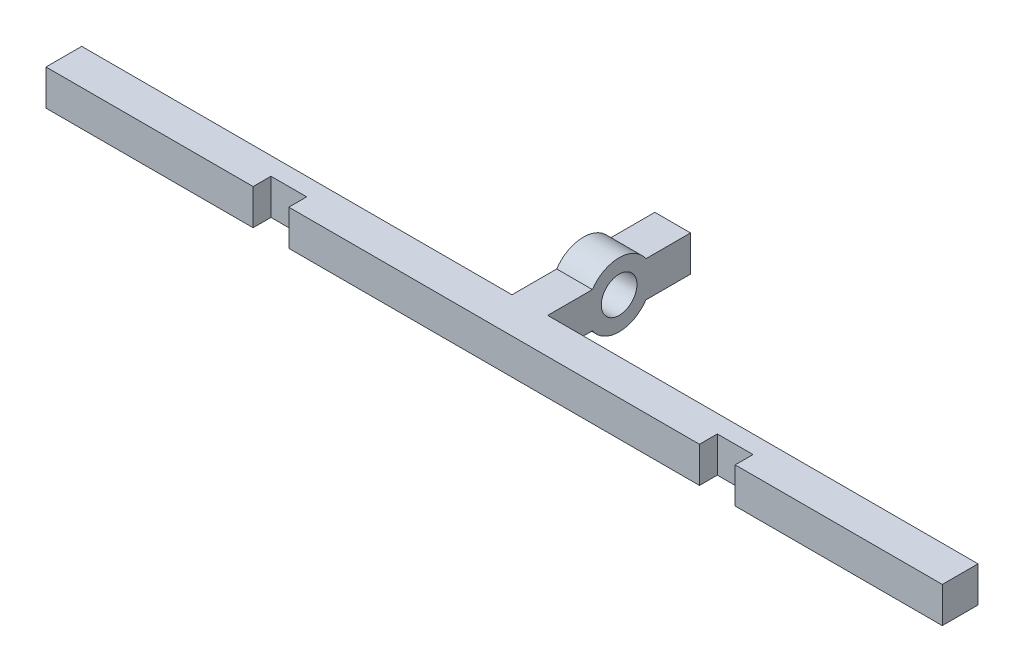
SolidWorks part; units mm, degrees
material "Alloy Steel"
ref_plane "Front Plane" through (0, 0, 0) normal (0, 0, 1) x (1, 0, 0)
ref_plane "Top Plane" through (0, 0, 0) normal (0, 1, 0) x (1, 0, 0)
ref_plane "Right Plane" through (0, 0, 0) normal (1, 0, 0) x (0, 0, -1)
ref_axis "X-Axis" through (-88.99, 0, 0) along (1, 0, 0)
ref_axis "Y-Axis" through (0, 55, 0) along (0, -1, 0)
ref_axis "Z-Axis" through (0, 0, -88.99) along (0, 0, 1)
sketch "Sketch1" plane through (0, 0, 0) normal (0, 0, 1) x (1, 0, 0)
  line L1 (0, 0) -> (-251, 0)
  line L2 (0, 0) -> (0, 10)
  line L3 (0, 10) -> (-251, 10)
  line L4 (-251, 0) -> (-251, 10)
  dimension "D1" = 10
  dimension "D2" = 251
extrude "Boss-Extrude1" add sketch "Sketch1" along normal blind 10
sketch "Sketch2" plane through (0, 0, 10) normal (0, 0, 1) x (1, 0, 0)
  line L0 (-251, 10) -> (-193, 10) construction
  line L1 (0, 10) -> (-251, 10) construction
  line L2 (-251, 0) -> (0, 0) construction
  line L3 (-193, 10) -> (-183, 10)
  line L4 (-193, 10) -> (-193, 0)
  line L5 (-193, 0) -> (-183, 0)
  line L6 (-183, 10) -> (-183, 0)
  line L7 (0, 10) -> (-58, 10) construction
  line L9 (-58, 10) -> (-68, 10)
  line L10 (-58, 10) -> (-58, 0)
  line L11 (-58, 0) -> (-68, 0)
  line L12 (-68, 10) -> (-68, 0)
  dimension "D1" = 115
extrude "Cut-Extrude1" cut sketch "Sketch2" against normal blind 5
sketch "Sketch4" plane through (0, 0, 0) normal (0, 0, -1) x (-1, 0, 0)
  line L0 (125.5, 0) -> (125.5, 10) construction
  line L1 (251, 0) -> (0, 0) construction
  line L2 (0, 10) -> (251, 10) construction
  line L4 (120.5, 0) -> (130.5, 0)
  line L5 (120.5, 0) -> (120.5, 10)
  line L6 (120.5, 10) -> (130.5, 10)
  line L7 (130.5, 0) -> (130.5, 10)
  line L8 (120.5, 0) -> (130.5, 10) construction
  line L9 (120.5, 10) -> (130.5, 0) construction
  point P6 (125.5, 5)
extrude "Boss-Extrude2" add sketch "Sketch4" along normal blind 40
sketch "Sketch5" plane through (-130.5, 0, 0) normal (-1, 0, 0) x (0, 0, 1)
  line L0 (0, 5) -> (-20, 5) construction
  line L3 (0, 0) -> (0, 10) construction
  circle A0 centre (-20, 5) radius 5
  dimension "D1" = 10
  dimension "D2" = 20
extrude "Cut-Extrude2" cut sketch "Sketch5" against normal up to next
sketch "Sketch7" plane through (-130.5, 0, 0) normal (-1, 0, 0) x (0, 0, 1)
  line L0 (-20, 0) -> (-20, 10) construction
  arc A0 (-20, 10) -> (-20, 0) centre (-20, 5) ccw construction
  circle A1 centre (-20, 5) radius 9
  circle A3 centre (-20, 5) radius 5
  dimension "D1" = 4
extrude "Boss-Extrude3" add sketch "Sketch7" against normal up to surface (10 mm away) up to face at (-120.5, 5, -8.75)
